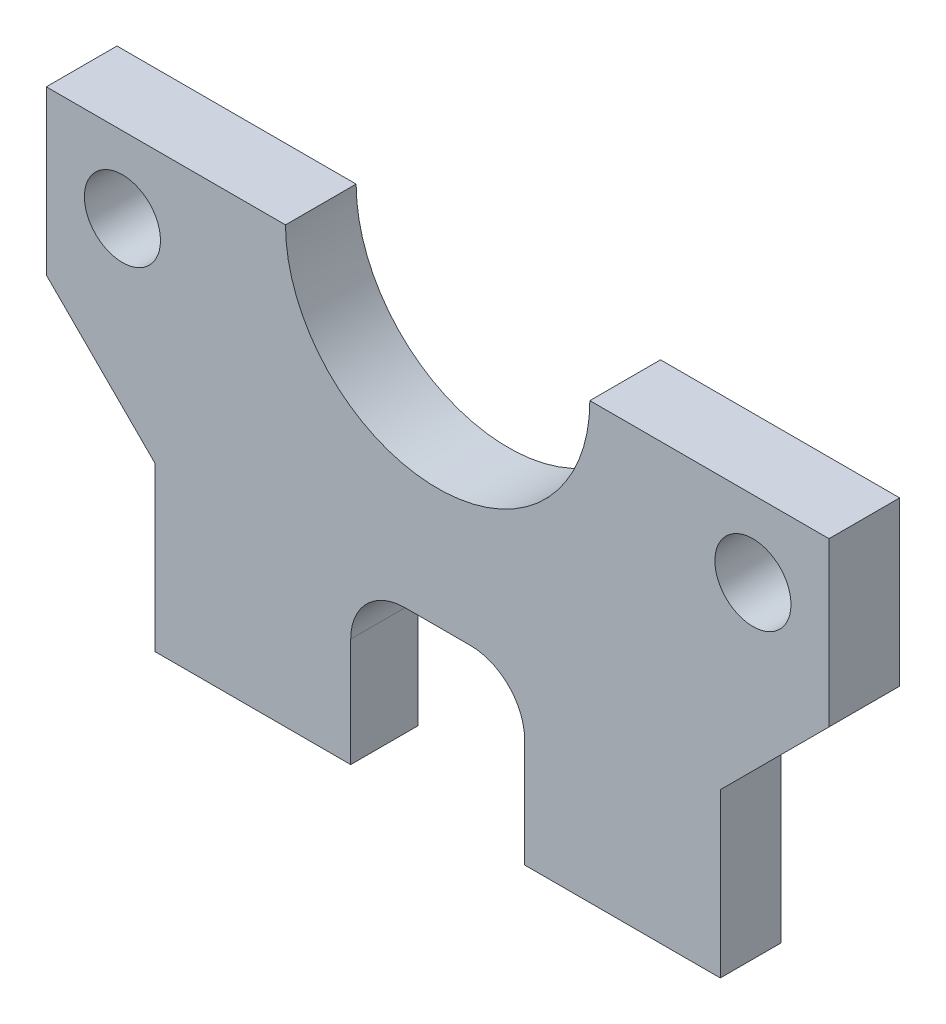
SolidWorks part; units mm, degrees
ref_plane "Front Plane" through (0, 0, 0) normal (0, 0, 1) x (1, 0, 0)
ref_plane "Top Plane" through (0, 0, 0) normal (0, 1, 0) x (1, 0, 0)
ref_plane "Right Plane" through (0, 0, 0) normal (1, 0, 0) x (0, 0, -1)
sketch "Sketch1" plane through (0, 0, 0) normal (0, 0, 1) x (1, 0, 0)
  line L1 (-26, -20) -> (26, -20)
  line L2 (-26, -20) -> (-26, 20)
  line L3 (-26, 20) -> (26, 20)
  line L4 (26, -20) -> (26, 20)
  line L5 (-26, -20) -> (26, 20) construction
  line L6 (-26, 20) -> (26, -20) construction
  point P0 (0, 0)
  dimension "D1" = 40
  dimension "D2" = 52
extrude "Boss-Extrude1" add sketch "Sketch1" along normal blind 6.5
sketch "Sketch16" plane through (0, 0, 0) normal (0, 0, -1) x (-1, 0, 0)
  line L1 (26, 20) -> (36, 20)
  line L2 (26, 20) -> (26, 5)
  line L3 (26, 5) -> (36, 5)
  line L4 (36, 20) -> (36, 5)
  line L5 (-26, 20) -> (-36, 20)
  line L6 (-26, 20) -> (-26, 5)
  line L7 (-26, 5) -> (-36, 5)
  line L8 (-36, 20) -> (-36, 5)
  dimension "D1" = 10
  dimension "D2" = 10
  dimension "D3" = 15
extrude "Boss-Extrude2" add sketch "Sketch16" against normal blind 6.5
chamfer "Chamfer1" distance 10 angle 45 2 edges at (26, 5, 3.25) (-26, 5, 3.25)
sketch "Sketch5" plane through (0, -20, 0) normal (0, -1, 0) x (1, 0, 0)
  line L0 (26, 0) -> (26, 0.9258)
  line L1 (26, 6.5) -> (26, 0) construction
  line L2 (26, 0.9258) -> (-26, 0)
  line L3 (-26, 0) -> (26, 0)
  dimension "D1" = 178.98
extrude "Cut-Extrude4" cut sketch "Sketch5" against normal blind 25
sketch "Sketch6" plane through (0, 0, 6.5) normal (0, 0, 1) x (1, 0, 0)
  line L0 (36, 20) -> (-36, 20) construction
  circle A0 centre (0, 20) radius 14
  dimension "D1" = 28
extrude "Cut-Extrude5" cut sketch "Sketch6" against normal blind 10
sketch "Sketch7" plane through (0, 0, 6.5) normal (0, 0, 1) x (1, 0, 0)
  line L0 (36, 20) -> (14, 20) construction
  line L1 (-14, 20) -> (-36, 20) construction
  line L4 (26, -5) -> (26, -20) construction
  line L5 (-26, -5) -> (-26, -20) construction
  circle A0 centre (29, 13) radius 3.5
  circle A1 centre (-29, 13) radius 3.5
  dimension "D1" = 7
  dimension "D2" = 7
  dimension "D4" = 3
  dimension "D5" = 7
  dimension "D6" = 7
  dimension "D3" = 3
extrude "Cut-Extrude6" cut sketch "Sketch7" against normal blind 10
sketch "Sketch14" plane through (0, -20, 0) normal (0, -1, 0) x (1, 0, 0)
  line L0 (-26, 6.5) -> (-26, 0) construction
  text T0 "Left"
  dimension "D1" = 1.5
  dimension "D2" = 1.5
extrude "Cut-Extrude8" cut sketch "Sketch14" against normal blind 1
sketch "Sketch15" plane through (0, 0, 6.5) normal (0, 0, 1) x (1, 0, 0)
  line L0 (-26, -20) -> (26, -20) construction
  line L1 (8, -20) -> (-8, -20)
  line L2 (8, -20) -> (8, -5)
  line L3 (8, -5) -> (-8, -5)
  line L4 (-8, -20) -> (-8, -5)
  line L5 (26, -20) -> (26, -5) construction
  point P6 (0, -20)
  point P7 (0, -20)
  dimension "D1" = 18
  dimension "D2" = 15
extrude "Cut-Extrude9" cut sketch "Sketch15" against normal blind 10
fillet "Fillet1" radius 5 2 edges at (-8, -5, 3.4102) (8, -5, 3.5527)
sketch "Sketch17" plane through (0, -20, 0) normal (0, -1, 0) x (1, 0, 0)
  line L0 (26, 0.9258) -> (36, 1.1039)
  line L1 (36, 6.5) -> (36, 0) construction
  line L2 (36, 1.1039) -> (36, 0)
  line L3 (36, 0) -> (26, 0)
  line L4 (26, 0) -> (26, 0.9258)
  line L5 (26, 0.9258) -> (8, 0.6053) construction
extrude "Cut-Extrude10" cut sketch "Sketch17" against normal blind 25
